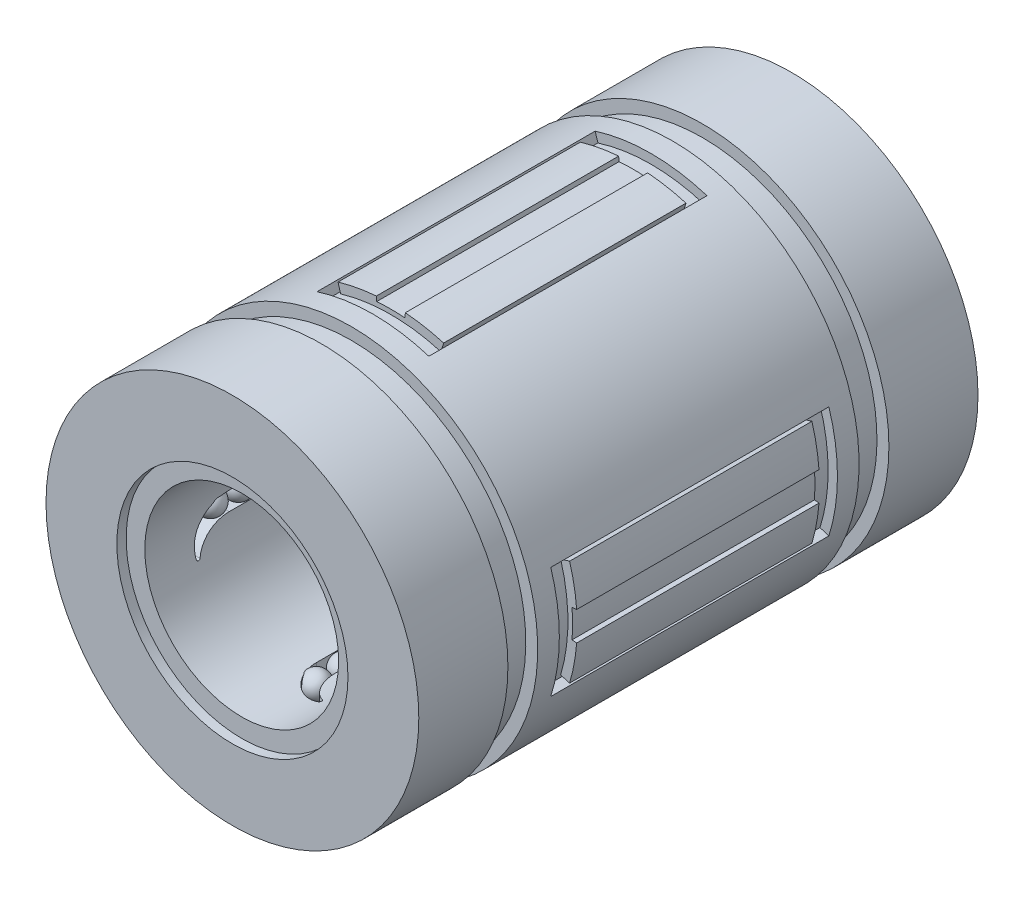
SolidWorks part; units mm, degrees
ref_plane "Front Plane" through (0, 0, 0) normal (0, 0, 1) x (1, 0, 0)
ref_plane "Top Plane" through (0, 0, 0) normal (0, 1, 0) x (1, 0, 0)
ref_plane "Right Plane" through (0, 0, 0) normal (1, 0, 0) x (0, 0, -1)
sketch "Sketch1" plane through (0, 0, 0) normal (0, 0, 1) x (1, 0, 0)
  line L0 (1.905, 6.0575) -> (1.8097, 5.7546)
  line L1 (-1.905, 6.0575) -> (-1.8097, 5.7546)
  line L2 (0, 0) -> (0, 6.35) construction
  line L3 (-3.2867, 0.3175) -> (-3.2867, -0.3175) construction
  line L4 (-3.9242, -0.3175) -> (-3.9242, 0.3175) construction
  line L5 (-3.2867, 0) -> (-3.9242, 0) construction
  line L6 (-3.6054, 0.4304) -> (-3.6054, -0.4304)
  line L7 (-1.799, 6.0898) -> (-1.709, 5.7853)
  line L8 (-0.4935, 6.3308) -> (-0.4812, 6.1725)
  line L9 (1.799, 6.0898) -> (1.709, 5.7853)
  line L10 (0.4935, 6.3308) -> (0.4812, 6.1725)
  line L11 (0, 19.05) -> (4.7236, 14.3264) construction
  line L12 (0, 19.05) -> (-4.7236, 14.3264) construction
  line L13 (4.7236, 14.3264) -> (4.9391, 14.1109)
  line L14 (-4.7236, 14.3264) -> (-4.9391, 14.1109)
  circle A0 centre (0, 0) radius 6.35
  arc A1 (1.8097, 5.7546) -> (-1.8097, 5.7546) centre (0, 0) ccw
  circle A2 centre (0, 0) radius 3.302
  circle A3 centre (0, 0) radius 3.175 construction
  circle A4 centre (0, 0) radius 3.937
  arc A5 (-3.6054, -0.4304) -> (-3.6054, 0.4304) centre (-3.6054, 0) ccw
  arc A7 (0.4812, 6.1725) -> (-0.4812, 6.1725) centre (0, 0) ccw
  arc A8 (4.7236, 14.3264) -> (-4.7236, 14.3264) centre (0, 19.05) ccw
  arc A9 (4.9391, 14.1109) -> (-4.9391, 14.1109) centre (0, 19.05) ccw
  dimension "OD" = 12.7
  dimension "ID" = 6.35
  dimension "Ring OD" = 13.97
  dimension "D1" = 3.81
  dimension "D2" = 0.3175
  dimension "D3" = 0.127
  dimension "D4" = 0.635
  dimension "D5" = 0.635
  dimension "D6" = 1
  dimension "D7" = 1
  dimension "D9" = 12
  dimension "D10" = 12
  dimension "D8" = 0.1588
  dimension "D11" = 90
  dimension "Offset" = 19.05
  dimension "D12" = 0.3048
sketch "Sketch2" plane through (0, 0, 0) normal (1, 0, 0) x (0, 0, -1)
  line L0 (9.525, 0) -> (-9.525, 0)
  line L1 (4.7371, 6.35) -> (-4.7371, 6.35)
  line L2 (5.9817, 6.35) -> (5.9817, 5.9436) construction
  line L3 (0, 7.0244) -> (0, -7.0244) construction
  line L4 (-6.35, -0.3175) -> (6.35, -0.3175)
  line L6 (-6.35, 0.3175) -> (6.35, 0.3175)
  line L8 (-6.35, -0.3175) -> (6.35, 0.3175) construction
  line L9 (-6.35, 0.3175) -> (6.35, -0.3175) construction
  line L11 (0, 6.35) -> (0, -6.35) construction
  line L13 (-6.4897, 6.35) -> (-5.4737, 6.35)
  line L14 (-6.4897, 6.35) -> (-6.4897, 5.9436)
  line L15 (-6.4897, 5.9436) -> (-5.4737, 5.9436)
  line L16 (-5.4737, 6.35) -> (-5.4737, 5.9436)
  line L17 (5.4737, 6.35) -> (6.4897, 6.35)
  line L18 (5.4737, 6.35) -> (5.4737, 5.9436)
  line L19 (5.4737, 5.9436) -> (6.4897, 5.9436)
  line L20 (6.4897, 6.35) -> (6.4897, 5.9436)
  arc A0 (6.35, 0.3175) -> (7.6182, -1.0193) centre (6.35, -0.9525) cw
  arc A1 (6.35, -0.3175) -> (7.4975, -1.0432) centre (6.35, -1.5875) cw
  arc A2 (7.4975, -1.0432) -> (7.6182, -1.0193) centre (7.5548, -1.016) ccw
  arc A3 (-6.35, 0.3175) -> (-7.6182, -1.0193) centre (-6.35, -0.9525) ccw
  arc A4 (-7.4975, -1.0432) -> (-7.6182, -1.0193) centre (-7.5548, -1.016) cw
  arc A5 (-6.35, -0.3175) -> (-7.4975, -1.0432) centre (-6.35, -1.5875) ccw
  point P0 (-9.2075, 0)
  point P4 (0, 0)
  point P9 (0, 6.35)
  point P10 (0, 0)
  point P20 (0, 0)
  point P37 (-4.1275, 6.35)
  point P38 (4.1275, 6.35)
  point P39 (5.5372, 6.35)
  point P40 (6.4262, 6.35)
  dimension "D4" = 0.635
  dimension "D5" = 1.27
  dimension "D6" = 1.27
  dimension "D7" = 0.0635
  dimension "Overall Length" = 19.05
  dimension "D1" = 9.4742
  dimension "D2" = 0.3175
  dimension "D3" = 6.35
  dimension "Groove Depth" = 0.4064
  dimension "C" = 12.9794
  dimension "D9" = 1.016
  dimension "D8" = 8.255
  dimension "D10" = 0.889
sketch "Sketch3" plane through (0, 0, 0) normal (0, 0, 1) x (1, 0, 0)
  circle A0 centre (0, 0) radius 6.35 construction
  circle A1 centre (0, 0) radius 3.302 construction
  circle A2 centre (0, 0) radius 6.35
  circle A3 centre (0, 0) radius 3.302
extrude "Boss-Extrude1" add sketch "Sketch3" along normal mid plane 19.05
sketch "Sketch4" plane through (0, 0, 9.525) normal (0, 0, 1) x (1, 0, 0)
  circle A0 centre (0, 0) radius 3.302 construction
  circle A1 centre (0, 0) radius 3.937 construction
  circle A2 centre (0, 0) radius 3.302
  circle A3 centre (0, 0) radius 3.937
extrude "Cut-Extrude1" cut sketch "Sketch4" against normal up to vertex (0.3175 mm away) up to point (0, 0, 9.2075)
mirror "Mirror1" about plane through (0, 0, 0) normal (0, 0, 1) of "Cut-Extrude1"
sketch "Sketch5" plane through (0, 0, 0) normal (0, 0, 1) x (1, 0, 0)
  line L0 (-1.905, 6.0575) -> (-1.8098, 5.7546) construction
  line L1 (1.905, 6.0575) -> (1.8097, 5.7546) construction
  line L2 (-1.905, 6.0575) -> (-1.8098, 5.7546)
  line L3 (1.905, 6.0575) -> (1.8097, 5.7546)
  circle A0 centre (0, 0) radius 6.35 construction
  arc A1 (1.8097, 5.7546) -> (-1.8098, 5.7546) centre (0, 0) ccw construction
  arc A2 (1.905, 6.0575) -> (-1.905, 6.0575) centre (0, 0) ccw
  arc A3 (1.8097, 5.7546) -> (-1.8098, 5.7546) centre (0, 0) ccw
extrude "Cut-Extrude2" cut sketch "Sketch5" against normal up to vertex (4.7371 mm away) and the other way up to vertex (4.7371 mm away) up to point (0, 6.35, -4.7371) other way up to point (0, 6.35, 4.7371)
sketch "Sketch6" plane through (0, 0, 0) normal (0, 0, 1) x (1, 0, 0)
  line L0 (1.799, 6.0898) -> (1.709, 5.7853) construction
  line L1 (0.4935, 6.3308) -> (0.4812, 6.1725) construction
  line L2 (-0.4935, 6.3308) -> (-0.4812, 6.1725) construction
  line L3 (-1.799, 6.0898) -> (-1.709, 5.7853) construction
  line L4 (1.799, 6.0898) -> (1.709, 5.7853)
  line L5 (0.4935, 6.3308) -> (0.4812, 6.1725)
  line L6 (-0.4935, 6.3308) -> (-0.4812, 6.1725)
  line L7 (-1.799, 6.0898) -> (-1.709, 5.7853)
  circle A0 centre (0, 0) radius 6.35 construction
  arc A1 (1.8097, 5.7546) -> (-1.8098, 5.7546) centre (0, 0) ccw construction
  arc A2 (0.4812, 6.1725) -> (-0.4812, 6.1725) centre (0, 0) ccw construction
  arc A3 (1.799, 6.0898) -> (0.4935, 6.3308) centre (0, 0) ccw
  arc A4 (1.709, 5.7853) -> (-1.709, 5.7853) centre (0, 0) ccw
  arc A5 (0.4812, 6.1725) -> (-0.4812, 6.1725) centre (0, 0) ccw
  arc A6 (-0.4935, 6.3308) -> (-1.799, 6.0898) centre (0, 0) ccw
extrude "Boss-Extrude2" add sketch "Sketch6" along normal up to vertex (4.1275 mm away) and the other way up to vertex (4.1275 mm away) up to point (0, 6.35, 4.1275) other way up to point (0, 6.35, -4.1275)
sketch "Sketch7" plane through (0, 0, 0) normal (1, 0, 0) x (0, 0, -1)
  line L0 (-6.35, -0.3175) -> (6.35, -0.3175) construction
  line L1 (-6.35, 0.3175) -> (6.35, 0.3175) construction
  line L2 (-6.35, -0.3175) -> (6.35, -0.3175)
  line L3 (-6.35, 0.3175) -> (6.35, 0.3175)
  arc A0 (7.4975, -1.0432) -> (6.35, -0.3175) centre (6.35, -1.5875) ccw construction
  arc A1 (7.4975, -1.0432) -> (7.6182, -1.0193) centre (7.5548, -1.016) ccw construction
  arc A2 (7.6182, -1.0193) -> (6.35, 0.3175) centre (6.35, -0.9525) ccw construction
  arc A3 (-6.35, 0.3175) -> (-7.6182, -1.0193) centre (-6.35, -0.9525) ccw construction
  arc A4 (-7.6182, -1.0193) -> (-7.4975, -1.0432) centre (-7.5548, -1.016) ccw construction
  arc A5 (-6.35, -0.3175) -> (-7.4975, -1.0432) centre (-6.35, -1.5875) ccw construction
  arc A6 (7.4975, -1.0432) -> (6.35, -0.3175) centre (6.35, -1.5875) ccw
  arc A7 (7.4975, -1.0432) -> (7.6182, -1.0193) centre (7.5548, -1.016) ccw
  arc A8 (7.6182, -1.0193) -> (6.35, 0.3175) centre (6.35, -0.9525) ccw
  arc A9 (-6.35, 0.3175) -> (-7.6182, -1.0193) centre (-6.35, -0.9525) ccw
  arc A10 (-7.6182, -1.0193) -> (-7.4975, -1.0432) centre (-7.5548, -1.016) ccw
  arc A11 (-6.35, -0.3175) -> (-7.4975, -1.0432) centre (-6.35, -1.5875) ccw
extrude "Cut-Extrude3" cut sketch "Sketch7" against normal up to surface (3.9242 mm away) up to face at (3.937, 0, 9.2075)
sketch "Sketch8" plane through (0, 0, 0) normal (0, 0, 1) x (1, 0, 0)
  line L0 (-3.6054, 0.4304) -> (-3.6054, -0.4304) construction
  line L1 (-3.6054, 0.4304) -> (-3.6054, -0.4304)
  arc A0 (-3.6054, -0.4304) -> (-3.6054, 0.4304) centre (-3.6054, 0) ccw construction
  arc A1 (-3.6054, -0.4304) -> (-3.6054, 0.4304) centre (-3.6054, 0) ccw
revolve "Revolve1" add sketch "Sketch8" angle 360 about L1
pattern_linear "LPattern1" count 8 spacing 0.9525 along (0, 0, -1) of "Revolve1"
mirror "Mirror2" about plane through (0, 0, 0) normal (0, 0, 1) of "LPattern1"
pattern_circular "CirPattern1" count 4 over 360 about axis through (0, 0, 9.525) along (0, 0, -1) of "Boss-Extrude2", "Cut-Extrude3", "Revolve1", "LPattern1", "Mirror2"
pattern_circular "CirPattern2" count 4 over 360 about axis through (0, 0, 9.525) along (0, 0, -1) of "Cut-Extrude2", "Boss-Extrude2" reverse direction yes
sketch "Sketch9" plane through (0, 0, 0) normal (1, 0, 0) x (0, 0, -1)
  line L0 (6.4897, 6.35) -> (6.4897, 5.9436) construction
  line L1 (5.4737, 5.9436) -> (6.4897, 5.9436) construction
  line L2 (5.4737, 6.35) -> (5.4737, 5.9436) construction
  line L3 (5.4737, 6.35) -> (6.4897, 6.35) construction
  line L4 (-5.4737, 6.35) -> (-5.4737, 5.9436) construction
  line L5 (-6.4897, 5.9436) -> (-5.4737, 5.9436) construction
  line L6 (-6.4897, 6.35) -> (-6.4897, 5.9436) construction
  line L7 (-6.4897, 6.35) -> (-5.4737, 6.35) construction
  line L8 (6.4897, 6.35) -> (6.4897, 5.9436)
  line L9 (5.4737, 5.9436) -> (6.4897, 5.9436)
  line L10 (5.4737, 6.35) -> (5.4737, 5.9436)
  line L11 (5.4737, 6.35) -> (6.4897, 6.35)
  line L12 (-5.4737, 6.35) -> (-5.4737, 5.9436)
  line L13 (-6.4897, 5.9436) -> (-5.4737, 5.9436)
  line L14 (-6.4897, 6.35) -> (-6.4897, 5.9436)
  line L15 (-6.4897, 6.35) -> (-5.4737, 6.35)
revolve "Cut-Revolve1" cut sketch "Sketch9" angle 360 about L0
ref_plane "Plane1" through (0, 0, -5.9817) normal (0, 0, -1) x (-1, 0, 0)
equation "\"D1@Sketch1\"=\"OD@Sketch1\"*.3"
equation "\"D2@Sketch1\"=\"OD@Sketch1\"*.025"
equation "\"D1@Sketch2\"=\"Overall Length@Sketch2\"* .4973333333"
equation "\"D4@Sketch1\"=\"OD@Sketch1\"*.05"
equation "\"D2@Sketch2\"=\"Overall Length@Sketch2\"* .01666667"
equation "\"D3@Sketch2\"=\"Overall Length@Sketch2\"* .333333333333"
equation "\"D4@Sketch2\"=\"OD@Sketch1\" * .05"
equation "\"D5@Sketch2\"=\"D3@Sketch2\"* .2"
equation "\"D6@Sketch2\"=\"D5@Sketch2\""
equation "\"D7@Sketch2\"=\"D6@Sketch2\"* .05"
equation "\"D5@Sketch1\"=\"OD@Sketch1\" * .05"
equation "\"D8@Sketch1\"=\"D2@Sketch1\"/2"
equation "\"D9@Sketch2\"=\"Overall Length@Sketch2\" * .0533333333"
equation "\"D1@Boss-Extrude1\"=\"Overall Length@Sketch2\""
equation "\"D8@Sketch2\"=\"Overall Length@Sketch2\" * .4333333333"
